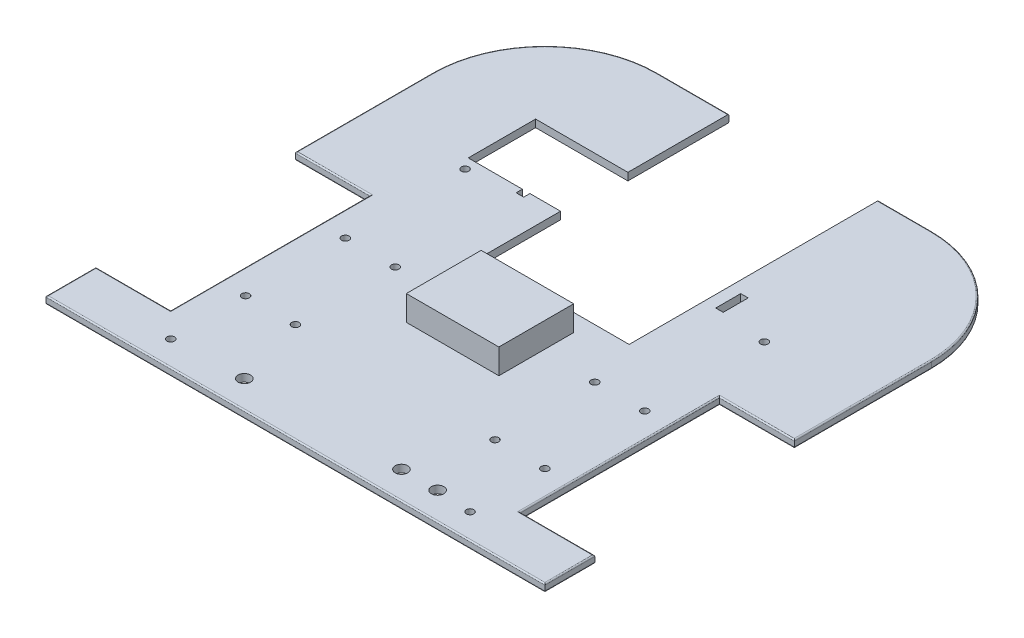
SolidWorks part; units mm, degrees
ref_plane "Front" through (0, 0, 0) normal (0, 0, 1) x (1, 0, 0)
ref_plane "Top" through (0, 0, 0) normal (0, 1, 0) x (1, 0, 0)
ref_plane "Right" through (0, 0, 0) normal (1, 0, 0) x (0, 0, -1)
sketch "Sketch1" plane through (0, 0, 0) normal (0, 1, 0) x (1, 0, 0)
  line L1 (100, -100) -> (-100, -100)
  line L2 (100, -100) -> (100, 100)
  line L3 (100, 100) -> (-100, 100)
  line L4 (-100, -100) -> (-100, 100)
  line L5 (100, -100) -> (-100, 100) construction
  line L6 (100, 100) -> (-100, -100) construction
  point P0 (0, 0)
  dimension "D1" = 200
  dimension "200mm" = 200
extrude "Boss-Extrude1" add sketch "Sketch1" along normal blind 3
ref_plane "Plane1" through (0, 0, 0) normal (1, 0, 0) x (0, 0, -1)
sketch "Sketch2" plane through (0, 3, 0) normal (0, 1, 0) x (1, 0, 0)
  line L0 (-100, 100) -> (-100, -100) construction
  line L1 (-70, 0) -> (-100, 0)
  line L2 (-70, 0) -> (-70, -80)
  line L3 (-70, -80) -> (-100, -80)
  line L4 (-100, 0) -> (-100, -80)
  line L5 (-100, -100) -> (100, -100) construction
  dimension "D1" = 20
  dimension "D2" = 30
  dimension "50" = 80
extrude "Cut-Extrude1" cut sketch "Sketch2" against normal through all and the other way blind 10
fillet "Fillet1" radius 45 2 edges at (100, 1.5, -100) (-100, 1.5, -100)
sketch "Sketch10" plane through (0, 3, 0) normal (0, 1, 0) x (1, 0, 0)
  line L0 (-100, -80) -> (-100, -100) construction
  line L1 (-100, -100) -> (100, -100) construction
  circle A0 centre (-60, -60) radius 1.5
  dimension "D1" = 3
  dimension "D2" = 40
  dimension "D3" = 40
extrude "Cut-Extrude9" cut sketch "Sketch10" against normal through all
pattern_linear "LPattern1" count 2 spacing 40 along (0, 0, -1) count 2 spacing 20 along (1, 0, 0) of "Cut-Extrude9"
sketch "Sketch13" plane through (0, 3, 0) normal (0, 1, 0) x (1, 0, 0)
  line L0 (-100, 55) -> (-100, 0) construction
  line L1 (55, 100) -> (-55, 100) construction
  line L3 (-41.5, 40) -> (-38.5, 40)
  line L4 (-41.5, 40) -> (-41.5, 30)
  line L5 (-41.5, 30) -> (-38.5, 30)
  line L6 (-38.5, 40) -> (-38.5, 30)
  line L7 (-41.5, 40) -> (-38.5, 30) construction
  line L8 (-41.5, 30) -> (-38.5, 40) construction
  circle A0 centre (-60, 28) radius 1.5
  point P7 (-40, 35)
  dimension "D1" = 3
  dimension "D2" = 40
  dimension "D3" = 72
  dimension "D4" = 10
  dimension "D5" = 3
  dimension "D6" = 65
  dimension "D7" = 60
extrude "Cut-Extrude10" cut sketch "Sketch13" against normal through all
sketch "Sketch14" plane through (0, 3, 0) normal (0, 1, 0) x (1, 0, 0)
  line L0 (-100, -80) -> (-100, -100) construction
  line L1 (-100, -100) -> (100, -100) construction
  circle A0 centre (-60, -90) radius 1.5
  dimension "D1" = 3
  dimension "D2" = 40
  dimension "D3" = 10
extrude "Cut-Extrude11" cut sketch "Sketch14" against normal through all
mirror "Mirror1" about plane through (0, 0, 0) normal (1, 0, 0) of "Cut-Extrude10", "Cut-Extrude9", "Cut-Extrude1", "LPattern1", "Cut-Extrude11"
fillet "Fillet2" radius 0.5 28 edges at (100, 3, -27.5) (86.8198, 3, -86.8198) (-100, 3, -27.5) (-86.8198, 3, -86.8198) (100, 0, 90) (85, 0, 80) (70, 0, 40) (85, 0, 0) (100, 0, -27.5) (86.8198, 0, -86.8198) (0, 0, -100) (-100, 0, -27.5) (-86.8198, 0, -86.8198) (-85, 0, 0) (-70, 0, 40) (-85, 0, 80) (-100, 0, 90) (0, 0, 100) (-85, 3, 80) (-100, 3, 90) (0, 3, 100) (100, 3, 90) (85, 3, 80) (70, 3, 40) (85, 3, 0) (-85, 3, 0) (-70, 3, 40) (0, 3, -100)
sketch "Sketch23" plane through (0, 3, 0) normal (0, 1, 0) x (1, 0, 0)
  line L1 (33.7796, 0) -> (-26.2204, 0)
  line L2 (33.7796, 0) -> (33.7796, 70)
  line L3 (33.7796, 70) -> (-26.2204, 70)
  line L4 (-26.2204, 0) -> (-26.2204, 70)
  line L5 (33.7796, 0) -> (-26.2204, 70) construction
  line L6 (33.7796, 70) -> (-26.2204, 0) construction
  point P0 (3.7796, 35)
  dimension "D1" = 60
  dimension "D2" = 70
  dimension "D3" = 35
extrude "Cut-Extrude13" cut sketch "Sketch23" against normal blind 10
sketch "Sketch25" plane through (0, 3, 0) normal (0, 1, 0) x (1, 0, 0)
  line L0 (-26.2204, 70) -> (-26.2204, 103)
  line L1 (-26.2204, 103) -> (33.7796, 103)
  line L2 (33.7796, 103) -> (33.7796, 70)
  line L3 (33.7796, 70) -> (-26.2204, 70)
  dimension "D1" = 60
  dimension "D2" = 33
extrude "Cut-Extrude15" cut sketch "Sketch25" against normal blind 10
sketch "Sketch26" plane through (0, 3, 0) normal (0, 1, 0) x (1, 0, 0)
  line L0 (100, 55) -> (100, 0) construction
  line L1 (18.5511, -37) -> (-18.5511, -37)
  line L2 (18.5511, -37) -> (18.5511, -7)
  line L3 (18.5511, -7) -> (-18.5511, -7)
  line L4 (-18.5511, -37) -> (-18.5511, -7)
  line L5 (18.5511, -37) -> (-18.5511, -7) construction
  line L6 (18.5511, -7) -> (-18.5511, -37) construction
  line L7 (-26.2204, 0) -> (33.7796, 0) construction
  point P0 (0, -22)
  dimension "D1" = 100
  dimension "D2" = 7
  dimension "D3" = 30
extrude "Boss-Extrude3" add sketch "Sketch26" along normal blind 10
sketch "Sketch27" plane through (0, 3, 0) normal (0, 1, 0) x (1, 0, 0)
  line L0 (-40.6102, 99.5) -> (-40.6102, 59.5)
  line L1 (-26.2204, 99.5) -> (-55, 99.5) construction
  line L2 (-26.2204, 99.5) -> (-26.2204, 0) construction
  line L3 (-26.2204, 59.5) -> (-63.2204, 59.5)
  line L4 (-26.2204, 59.5) -> (-26.2204, 32.5)
  line L5 (-26.2204, 32.5) -> (-63.2204, 32.5)
  line L6 (-63.2204, 59.5) -> (-63.2204, 32.5)
  line L7 (-55, 100) -> (-26.2204, 100) construction
  dimension "D1" = 40
  dimension "D2" = 37
  dimension "D3" = 27
  dimension "D4" = 40.5
extrude "Cut-Extrude16" cut sketch "Sketch27" against normal blind 10 contours L6 L5 L4 L3
sketch "Sketch30" plane through (0, 3, 0) normal (0, 1, 0) x (1, 0, 0)
  line L0 (-99.5, -89) -> (-31.5, -89) construction
  line L1 (-99.5, -80.5) -> (-99.5, -99.5) construction
  line L2 (-31.5, -89) -> (-31.5, -99.5)
  line L3 (-99.5, -99.5) -> (99.5, -99.5) construction
  line L5 (0, -50) -> (0, 50) construction
  line L6 (-69.5, -80.5) -> (-99.5, -80.5) construction
  line L7 (-31.5, -89) -> (46, -89) construction
  circle A0 centre (-31.5, -89) radius 2.5
  circle A1 centre (31.5, -89) radius 2.5
  circle A2 centre (46, -89) radius 2.5
  dimension "D2" = 5
  dimension "D5" = 5
  dimension "D1" = 68
  dimension "D3" = 8.5
  dimension "D4" = 77.5
extrude "Cut-Extrude17" cut sketch "Sketch30" against normal blind 10 contours A0 | A1
sketch "Sketch31" plane through (0, 3, 0) normal (0, 1, 0) x (1, 0, 0)
  line L0 (-31.5, -89) -> (46, -89) construction
  circle A0 centre (46, -89) radius 2.5
  dimension "D2" = 5
  dimension "D1" = 77.5
extrude "Cut-Extrude18" cut sketch "Sketch31" against normal blind 10
